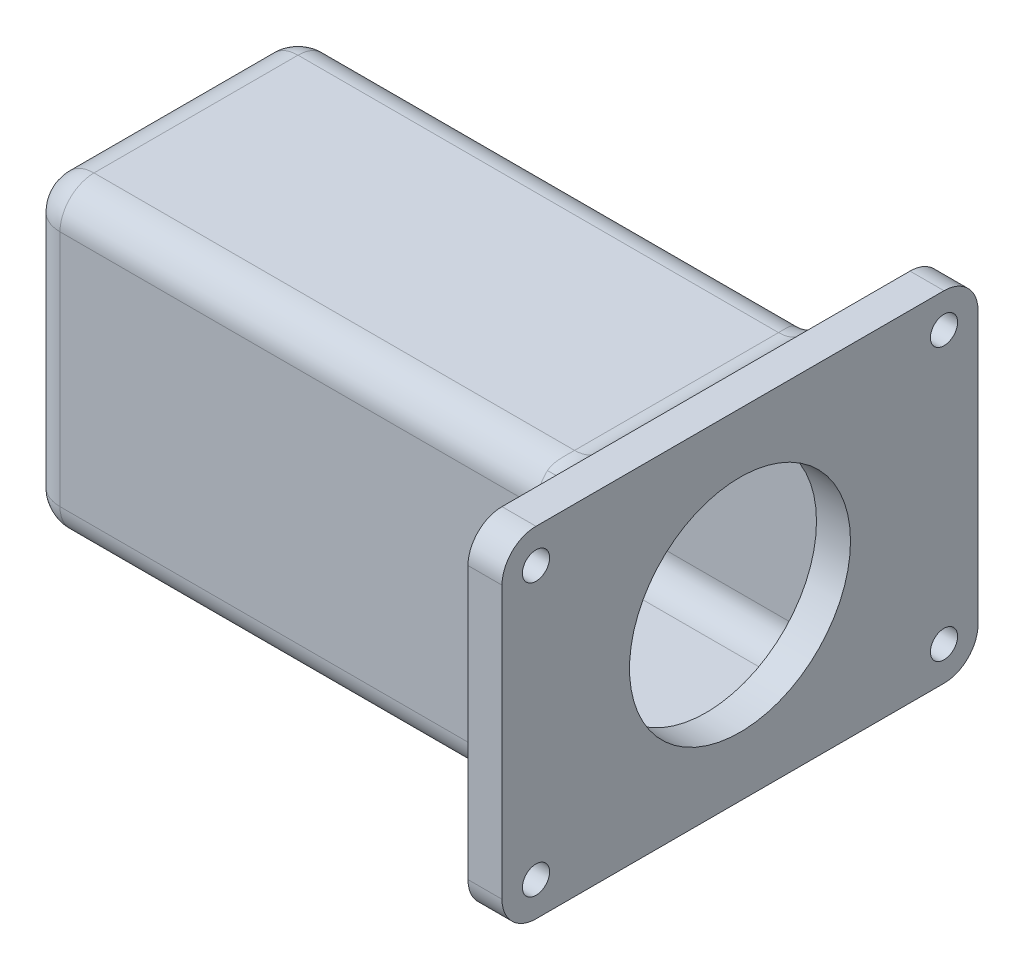
SolidWorks part; units mm, degrees
ref_plane "Front Plane" through (0, 0, 0) normal (0, 0, 1) x (1, 0, 0)
ref_plane "Top Plane" through (0, 0, 0) normal (0, 1, 0) x (1, 0, 0)
ref_plane "Right Plane" through (0, 0, 0) normal (1, 0, 0) x (0, 0, -1)
sketch "Sketch1" plane through (0, 0, 0) normal (1, 0, 0) x (0, 0, -1)
  line L1 (-40, -45) -> (40, -45)
  line L2 (-40, -45) -> (-40, 45)
  line L3 (-40, 45) -> (40, 45)
  line L4 (40, -45) -> (40, 45)
  line L5 (-40, -45) -> (40, 45) construction
  line L6 (-40, 45) -> (40, -45) construction
  point P0 (0, 0)
  dimension "D1" = 90
  dimension "D2" = 80
extrude "Boss-Extrude1" add sketch "Sketch1" along normal blind 160
fillet "Fillet1" radius 10 8 edges at (0, -45, 0) (0, 0, -40) (0, 0, 40) (0, 45, 0) (80, -45, -40) (80, -45, 40) (80, 45, 40) (80, 45, -40)
shell "Shell1" thickness 2 removed face at (160, 0, 0)
sketch "Sketch2" plane through (160, 0, 0) normal (1, 0, 0) x (0, 0, -1)
  line L0 (0, 32.5) -> (0, 0) construction
  line L1 (-60, -50) -> (60, -50)
  line L2 (-70, -40) -> (-70, 40)
  line L3 (-60, 50) -> (60, 50)
  line L4 (70, -40) -> (70, 40)
  line L5 (-70, -50) -> (70, 50) construction
  line L6 (-70, 50) -> (70, -50) construction
  line L7 (0, 0) -> (32.5, 0) construction
  circle A0 centre (0, 0) radius 32.5
  arc A2 (60, -50) -> (70, -40) centre (60, -40) ccw
  arc A3 (-70, 40) -> (-60, 50) centre (-60, 40) cw
  arc A4 (-60, -50) -> (-70, -40) centre (-60, -40) cw
  arc A5 (60, 50) -> (70, 40) centre (60, 40) cw
  circle A6 centre (60, 40) radius 4
  circle A7 centre (-60, 40) radius 4
  circle A8 centre (-60, -40) radius 4
  circle A9 centre (60, -40) radius 4
  point P0 (0, 0)
  dimension "D1" = 10
  dimension "D4" = 65
  dimension "D5" = 8
  dimension "D2" = 100
  dimension "D3" = 140
  dimension "D6" = 40
  dimension "D7" = 60
extrude "Boss-Extrude2" add sketch "Sketch2" along normal blind 10
fillet "Fillet2" radius 10 6 edges at (160, 42.0711, -37.0711) (160, 0, -40) (160, -42.0711, -37.0711) (160, -42.0711, 37.0711) (160, 0, 40) (160, 42.0711, 37.0711)
